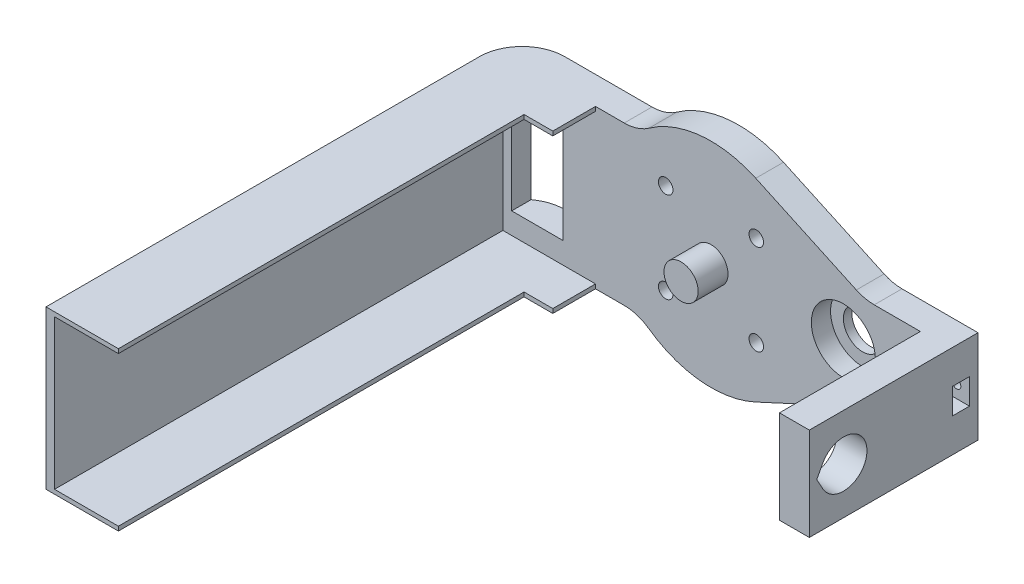
SolidWorks part; units mm, degrees
ref_plane "Front Plane" through (0, 0, 0) normal (0, 0, 1) x (1, 0, 0)
ref_plane "Top Plane" through (0, 0, 0) normal (0, 1, 0) x (1, 0, 0)
ref_plane "Right Plane" through (0, 0, 0) normal (1, 0, 0) x (0, 0, -1)
sketch "Sketch1" plane through (0, 0, 0) normal (0, 0, 1) x (1, 0, 0)
  line L0 (10.4839, 22.6956) -> (36.0323, 10.8939)
  line L1 (36.0323, -10.8939) -> (10.4839, -22.6956)
  circle A0 centre (0, 0) radius 22.215 construction
  circle A1 centre (31, 0) radius 10.2 construction
  arc A2 (10.4839, 22.6956) -> (10.4839, -22.6956) centre (0, 0) ccw
  arc A3 (36.0323, -10.8939) -> (36.0323, 10.8939) centre (31, 0) ccw
  dimension "D1" = 20.4
  dimension "D2" = 44.43
  dimension "D4" = 25
  dimension "D5" = 12
  dimension "D3" = 31
extrude "Boss-Extrude1" add sketch "Sketch1" along normal blind 4.5
sketch "Sketch2" plane through (0, 0, 4.5) normal (0, 0, 1) x (1, 0, 0)
  circle A0 centre (31, 0) radius 7.5
  dimension "D1" = 15
extrude "Cut-Extrude1" cut sketch "Sketch2" against normal through all
sketch "Sketch3" plane through (0, 0, 4.5) normal (0, 0, 1) x (1, 0, 0)
  circle A0 centre (0, 0) radius 4
  dimension "D1" = 8
extrude "Boss-Extrude2" add sketch "Sketch3" along normal blind 7
sketch "Sketch4" plane through (0, 0, 0) normal (0, 0, -1) x (-1, 0, 0)
  line L0 (-36.0323, 10.8939) -> (-56.0323, 10.8939)
  line L1 (-36.0323, -10.8939) -> (-56.0323, -10.8939)
  line L2 (-56.0323, -10.8939) -> (-56.0323, 10.8939)
  line L3 (22.5016, 10.8939) -> (42.5016, 10.8939)
  line L4 (42.5016, 10.8939) -> (42.5016, -10.8939)
  line L5 (42.5016, -10.8939) -> (22.5016, -10.8939)
  arc A0 (-10.4839, -22.6956) -> (-10.4839, 22.6956) centre (0, 0) ccw construction
  arc A1 (22.5016, -10.8939) -> (22.5016, 10.8939) centre (0, 0) ccw
  arc A2 (-36.0323, 10.8939) -> (-36.0323, -10.8939) centre (-31, 0) ccw construction
  arc A3 (-36.0323, 10.8939) -> (-36.0323, -10.8939) centre (-31, 0) ccw
  dimension "D1" = 20
  dimension "D2" = 20
extrude "Boss-Extrude3" add sketch "Sketch4" against normal up to surface (4.5 mm away) up to face at (4, 0, 4.5)
fillet "Fillet1" radius 10 4 edges at (-42.5016, 10.8939, 2.25) (-42.5016, -10.8939, 2.25) (56.0323, -10.8939, 2.25) (56.0323, 10.8939, 2.25)
sketch "Sketch8" plane through (0, 0, 4.5) normal (0, 0, 1) x (1, 0, 0)
  line L0 (56.0323, 0.8939) -> (56.0323, -0.8939) construction
  line L2 (56.0323, 0.8939) -> (56.0323, -0.8939)
  line L3 (55.4014, -4.3896) -> (55.4014, 4.3896)
  line L4 (-42.5016, -0.8939) -> (-42.5016, 0.8939) construction
  line L6 (-42.5016, -0.8939) -> (-42.5016, 0.8939)
  line L7 (-41.8707, 4.3896) -> (-41.8707, -4.3896)
  arc A0 (56.0323, 0.8939) -> (46.0323, 10.8939) centre (46.0323, 0.8939) ccw construction
  arc A1 (46.0323, -10.8939) -> (56.0323, -0.8939) centre (46.0323, -0.8939) ccw construction
  arc A2 (56.0323, 0.8939) -> (55.4014, 4.3896) centre (46.0323, 0.8939) ccw
  arc A3 (55.4014, -4.3896) -> (56.0323, -0.8939) centre (46.0323, -0.8939) ccw
  arc A4 (-32.5016, 10.8939) -> (-42.5016, 0.8939) centre (-32.5016, 0.8939) ccw construction
  arc A5 (-42.5016, -0.8939) -> (-32.5016, -10.8939) centre (-32.5016, -0.8939) ccw construction
  arc A6 (-41.8707, 4.3896) -> (-42.5016, 0.8939) centre (-32.5016, 0.8939) ccw
  arc A7 (-42.5016, -0.8939) -> (-41.8707, -4.3896) centre (-32.5016, -0.8939) ccw
extrude "Cut-Extrude4" cut sketch "Sketch8" against normal through all
sketch "Sketch9" plane through (0, 0, 4.5) normal (0, 0, 1) x (1, 0, 0)
  circle A0 centre (0, 0) radius 15 construction
  circle A1 centre (-10.6066, 10.6066) radius 1
  circle A2 centre (10.6066, 10.6066) radius 1
  circle A3 centre (10.6066, -10.6066) radius 1
  circle A4 centre (-10.6066, -10.6066) radius 1
  point P14 (0, 0)
  dimension "D1" = 30
  dimension "D2" = 2
  dimension "D3" = 4
extrude "Cut-Extrude5" cut sketch "Sketch9" against normal through all
sketch "Sketch10" plane through (0, 0, 4.5) normal (0, 0, 1) x (1, 0, 0)
  circle A0 centre (-10.6066, 10.6066) radius 1.7
  circle A1 centre (10.6066, 10.6066) radius 1.7
  circle A2 centre (10.6066, -10.6066) radius 1.7
  circle A3 centre (-10.6066, -10.6066) radius 1.7
  dimension "D1" = 3.4
extrude "Cut-Extrude6" cut sketch "Sketch10" against normal blind 2.4
sketch "Sketch11" plane through (0, 0, 0) normal (0, 0, -1) x (-1, 0, 0)
  line L0 (-40.9602, 14.6461) -> (-73.6718, 18.9155)
  line L1 (-73.6718, 18.9155) -> (-68.6403, -15.6759)
  line L2 (-68.6403, -15.6759) -> (-41.445, -13.2122)
  arc A0 (-40.9602, 14.6461) -> (-41.445, -13.2122) centre (0, 0) ccw
  dimension "D1" = 87
extrude "Cut-Extrude7" cut sketch "Sketch11" against normal up to surface (4.5 mm away) up to face at (-8.9066, -10.6066, 4.5)
fillet "Fillet2" radius 10 2 edges at (42.1138, -10.8939, 2.25) (42.1138, 10.8939, 2.25)
sketch "Sketch12" plane through (0, 0, 4.5) normal (0, 0, 1) x (1, 0, 0)
  line L0 (-22.5016, 10.8939) -> (-42.5927, 14.8195)
  line L1 (-42.5927, 14.8195) -> (-48.1481, -13.6126)
  line L2 (-48.1481, -13.6126) -> (-27.4273, -14.3153)
  line L3 (-27.4273, -14.3153) -> (-22.5016, -10.8939)
  arc A0 (-22.5016, 10.8939) -> (-22.5016, -10.8939) centre (0, 0) ccw
extrude "Cut-Extrude8" cut sketch "Sketch12" against normal through all
sketch "Sketch23" plane through (0, 0, 0) normal (0, 0, -1) x (-1, 0, 0)
  line L2 (-36.0323, -10.8939) -> (-10.4839, -22.6956)
  line L3 (-10.4839, 22.6956) -> (-36.0323, 10.8939)
  line L4 (-36.0323, -10.8939) -> (-10.4839, -22.6956)
  line L5 (-10.4839, 22.6956) -> (-36.0323, 10.8939)
  circle A0 centre (-10.6066, -10.6066) radius 1 construction
  circle A1 centre (10.6066, -10.6066) radius 1 construction
  circle A2 centre (10.6066, 10.6066) radius 1 construction
  circle A3 centre (-10.6066, 10.6066) radius 1 construction
  arc A4 (-10.4839, -22.6956) -> (-10.4839, 22.6956) centre (0, 0) ccw
  arc A5 (-36.0323, 10.8939) -> (-43.4709, 1.5916) centre (-33.4776, 1.2257) ccw
  arc A6 (-43.4709, 1.5916) -> (-43.4709, -1.5916) centre (0, 0) ccw
  arc A7 (-43.4709, -1.5916) -> (-36.0323, -10.8939) centre (-33.4776, -1.2257) ccw
  arc A8 (-10.4839, -22.6956) -> (-10.4839, 22.6956) centre (0, 0) ccw
  arc A9 (-36.0323, 10.8939) -> (-43.4709, 1.5916) centre (-33.4776, 1.2257) ccw
  arc A10 (-43.4709, 1.5916) -> (-43.4709, -1.5916) centre (0, 0) ccw
  arc A11 (-43.4709, -1.5916) -> (-36.0323, -10.8939) centre (-33.4776, -1.2257) ccw
  circle A12 centre (-10.6066, -10.6066) radius 1
  circle A13 centre (10.6066, -10.6066) radius 1
  circle A14 centre (10.6066, 10.6066) radius 1
  circle A15 centre (-10.6066, 10.6066) radius 1
  circle A16 centre (-31, 0) radius 4.5
  dimension "D2" = 9
  dimension "D1" = 0
extrude "Boss-Extrude6" add sketch "Sketch23" along normal blind 2
sketch "Sketch24" plane through (0, 0, -2) normal (0, 0, -1) x (-1, 0, 0)
  line L0 (-10.6066, 10.6066) -> (10.6066, 10.6066) construction
ref_axis "Axis1" through (10.6066, 10.6066, -2) along (-1, 0, 0)
sketch "Sketch25" plane through (0, 0, -2) normal (0, 0, -1) x (-1, 0, 0)
  line L1 (-36.0323, 10.8939) -> (-56.0323, 10.8939)
  line L3 (-36.0323, -10.8939) -> (-56.0323, -10.8939)
  line L4 (-56.0323, 10.8939) -> (-56.0323, -10.8939)
  arc A0 (-43.4709, -1.5916) -> (-36.0323, -10.8939) centre (-33.4776, -1.2257) ccw construction
  arc A1 (-43.4709, 1.5916) -> (-43.4709, -1.5916) centre (0, 0) ccw construction
  arc A2 (-36.0323, 10.8939) -> (-43.4709, 1.5916) centre (-33.4776, 1.2257) ccw construction
  arc A3 (-43.4709, -1.5916) -> (-36.0323, -10.8939) centre (-33.4776, -1.2257) ccw
  arc A4 (-43.4709, 1.5916) -> (-43.4709, -1.5916) centre (0, 0) ccw
  arc A5 (-36.0323, 10.8939) -> (-43.4709, 1.5916) centre (-33.4776, 1.2257) ccw
  dimension "D1" = 20
extrude "Boss-Extrude7" add sketch "Sketch25" against normal up to surface (6.5 mm away) up to face at (24.5985, 0, 4.5)
sketch "Sketch26" plane through (0, 0, 4.5) normal (0, 0, 1) x (1, 0, 0)
  line L0 (36.0323, 10.8939) -> (56.0323, 10.8939) construction
  line L1 (56.0323, -10.8939) -> (47.0323, -10.8939)
  line L2 (56.0323, -10.8939) -> (56.0323, 10.8939)
  line L3 (56.0323, 10.8939) -> (47.0323, 10.8939)
  line L4 (47.0323, -10.8939) -> (47.0323, 10.8939)
  dimension "D1" = 9
extrude "Boss-Extrude8" add sketch "Sketch26" along normal blind 33
sketch "Sketch27" plane through (56.0323, 0, 0) normal (1, 0, 0) x (0, 0, -1)
  circle A0 centre (-29.5, 0) radius 5
extrude "Cut-Extrude9" cut sketch "Sketch27" against normal up to next
sketch "Sketch28" plane through (0, 0, -2) normal (0, 0, -1) x (-1, 0, 0)
  line L1 (16.8152, 18.5) -> (50.7321, 18.5)
  line L3 (16.8152, -18.5) -> (50.7321, -18.5)
  line L4 (0, 0) -> (54, 0) construction
  line L5 (54, 0) -> (25.875, 18.5) construction
  line L6 (54, 0) -> (31.6196, -18.5) construction
  line L7 (50.7321, -18.5) -> (25, 0) construction
  line L8 (25, 0) -> (50.7321, 18.5) construction
  line L9 (50.7321, 18.5) -> (50.7321, -18.5)
  arc A0 (50.7321, -18.5) -> (50.7321, 18.5) centre (0, 0) ccw construction
  arc A2 (-10.4839, -22.6956) -> (-10.4839, 22.6956) centre (0, 0) ccw construction
  arc A3 (16.8152, -18.5) -> (16.8152, 18.5) centre (0, 0) ccw
  dimension "D1" = 108
  dimension "D3" = 37
extrude "Boss-Extrude9" add sketch "Sketch28" against normal up to surface (6.5 mm away) up to face at (38.5, 0, 4.5)
sketch "Sketch29" plane through (0, 0, 4.5) normal (0, 0, 1) x (1, 0, 0)
  line L0 (-50.7321, 18.5) -> (-33.7737, 18.5)
  line L1 (-50.7321, 18.5) -> (-50.7321, -18.5)
  line L2 (-50.7321, -18.5) -> (-33.7737, -18.5)
  line L3 (-16.8152, -18.5) -> (-50.7321, -18.5) construction
  line L4 (-50.7321, 18.5) -> (-16.8152, 18.5) construction
  line L5 (-48.7321, 16.5) -> (-48.7321, -16.5)
  line L6 (-48.7321, 16.5) -> (-50.7321, 18.5) construction
  line L7 (-48.7321, -16.5) -> (-50.7321, -18.5) construction
  line L8 (-48.7321, 16.5) -> (-33.7737, 16.5)
  line L9 (-33.7737, 16.5) -> (-33.7737, 18.5)
  line L10 (-33.7737, -18.5) -> (-33.7737, -16.5)
  line L11 (-33.7737, -16.5) -> (-48.7321, -16.5)
  dimension "D1" = 33
  dimension "D2" = 2
extrude "Boss-Extrude10" add sketch "Sketch29" along normal blind 105
fillet "Fillet3" radius 10 1 edges at (-50.7321, 0, -2)
fillet "Fillet4" radius 10 4 edges at (36.0323, 10.8939, 1.25) (36.0323, -10.8939, 1.25) (-16.8152, 18.5, 1.25) (-16.8152, -18.5, 1.25)
sketch "Sketch30" plane through (56.0323, 0, 0) normal (1, 0, 0) x (0, 0, -1)
  line L0 (-34.1928, 1.7255) -> (-34.8273, 0)
  line L1 (-34.8273, 0) -> (-34.1928, -1.7255)
  line L2 (-34.5, 0) -> (-34.8273, 0) construction
  circle A0 centre (-29.5, 0) radius 5 construction
  arc A1 (-34.1928, 1.7255) -> (-34.1928, -1.7255) centre (-29.5, 0) ccw
extrude "Cut-Extrude10" cut sketch "Sketch30" against normal up to surface (9 mm away) up to face at (47.0323, 0, 24.5)
sketch "Sketch31" plane through (0, 0, 4.5) normal (0, 0, 1) x (1, 0, 0)
  line L0 (-46.6706, 12.5) -> (-48.7321, 16.5) construction
  line L1 (-46.6706, 12.5) -> (-34.6706, 12.5)
  line L2 (-46.6706, 12.5) -> (-46.6706, -12.5)
  line L3 (-46.6706, -12.5) -> (-34.6706, -12.5)
  line L4 (-34.6706, 12.5) -> (-34.6706, -12.5)
  line L5 (-46.6706, -12.5) -> (-48.7321, -16.5) construction
  dimension "D1" = 25
  dimension "D2" = 12
  dimension "D3" = 4.5
extrude "Cut-Extrude11" cut sketch "Sketch31" against normal through all
sketch "Sketch32" plane through (0, 0, 4.5) normal (0, 0, 1) x (1, 0, 0)
  line L0 (-33.7737, 18.5) -> (-33.7737, 16.5)
  line L1 (-33.7737, 16.5) -> (-27.7321, 16.5)
  line L2 (-27.7321, 16.5) -> (-27.7321, -16.5)
  line L3 (-27.7321, -16.5) -> (-33.7737, -16.5)
  line L4 (-33.7737, -16.5) -> (-33.7737, -18.5)
  line L5 (-33.7737, -18.5) -> (-27.045, -18.5)
  line L6 (-20.3162, -18.5) -> (-33.7737, -18.5) construction
  line L7 (-27.045, -18.5) -> (-27.045, 18.5)
  line L8 (-33.7737, 18.5) -> (-20.3162, 18.5) construction
  line L9 (-27.045, 18.5) -> (-33.7737, 18.5)
extrude "Boss-Extrude11" add sketch "Sketch32" along normal blind 10
sketch "Sketch33" plane through (-27.045, 0, 0) normal (1, 0, 0) x (0, 0, -1)
  line L0 (-4.5, -22.6956) -> (-4.5, -11.8156) construction
  line L1 (-14.5, 16.5) -> (-4.5, 16.5)
  line L2 (-14.5, 16.5) -> (-14.5, -16.5)
  line L3 (-14.5, -16.5) -> (-4.5, -16.5)
  line L4 (-4.5, 16.5) -> (-4.5, -16.5)
  line L5 (-109.5, -16.5) -> (-4.5, -16.5) construction
extrude "Cut-Extrude12" cut sketch "Sketch33" against normal up to next
sketch "Sketch34" plane through (-48.7321, 0, 0) normal (1, 0, 0) x (0, 0, -1)
  line L0 (-109.5, 16.5) -> (-109.5, 18.5) construction
  line L1 (-109.5, 17.5) -> (-4.5, 17.5)
  line L2 (-109.5, 17.5) -> (-109.5, -17.5)
  line L3 (-109.5, -17.5) -> (-4.5, -17.5)
  line L4 (-4.5, 17.5) -> (-4.5, -17.5)
  line L5 (-4.5, -18.5) -> (-4.5, -16.5) construction
extrude "Cut-Extrude13" cut sketch "Sketch34" along normal up to surface (21.6872 mm away) up to face at (-27.045, -17.5, 9.5)
sketch "Sketch35" plane through (56.0323, 0, 0) normal (1, 0, 0) x (0, 0, -1)
  circle A0 centre (-29.5, 0) radius 5.5
  dimension "D1" = 11
extrude "Cut-Extrude14" cut sketch "Sketch35" against normal up to next
sketch "Sketch36" plane through (56.0323, 0, 0) normal (1, 0, 0) x (0, 0, -1)
  line L0 (-34.3284, 2.6337) -> (-35.765, 0)
  line L1 (-35.765, 0) -> (-34.3284, -2.6337)
  line L2 (-35.765, 0) -> (0, 0) construction
  circle A0 centre (-29.5, 0) radius 5.5 construction
  arc A1 (-34.3284, -2.6337) -> (-34.3284, 2.6337) centre (-29.5, 0) cw
  dimension "D1" = 3
extrude "Cut-Extrude15" cut sketch "Sketch36" against normal up to next
sketch "Sketch37" plane through (0, 0, 37.5) normal (0, 0, 1) x (1, 0, 0)
  line L0 (47.0323, -10.8939) -> (56.0323, -10.8939) construction
  line L1 (47.0323, 10.8939) -> (49.0323, 10.8939)
  line L2 (47.0323, 10.8939) -> (47.0323, -10.8939)
  line L3 (47.0323, -10.8939) -> (49.0323, -10.8939)
  line L4 (49.0323, 10.8939) -> (49.0323, -10.8939)
  dimension "D1" = 2
extrude "Cut-Extrude16" cut sketch "Sketch37" against normal up to surface (33 mm away) up to face at (-0.8985, 0, 4.5)
sketch "Sketch38" plane through (56.0323, 0, 0) normal (1, 0, 0) x (0, 0, -1)
  line L0 (2, 0) -> (-49.9072, 0) construction
  line L1 (2, 10.8099) -> (2, -10.8099) construction
  line L2 (-4, 3) -> (0, 0) construction
  line L7 (-4, 3) -> (0, 3)
  line L8 (-4, 3) -> (-4, -3)
  line L9 (-4, -3) -> (0, -3)
  line L10 (0, 3) -> (0, -3)
  line L11 (0, 0) -> (-4, -3) construction
  dimension "D1" = 2
  dimension "D2" = 4
  dimension "D3" = 6
extrude "Cut-Extrude17" cut sketch "Sketch38" against normal blind 6
sketch "Sketch39" plane through (0, 0, -2) normal (0, 0, -1) x (-1, 0, 0)
  circle A0 centre (-53.0161, 0) radius 1
extrude "Cut-Extrude18" cut sketch "Sketch39" against normal up to surface (6 mm away) up to face at (53.0323, 0, 4)
